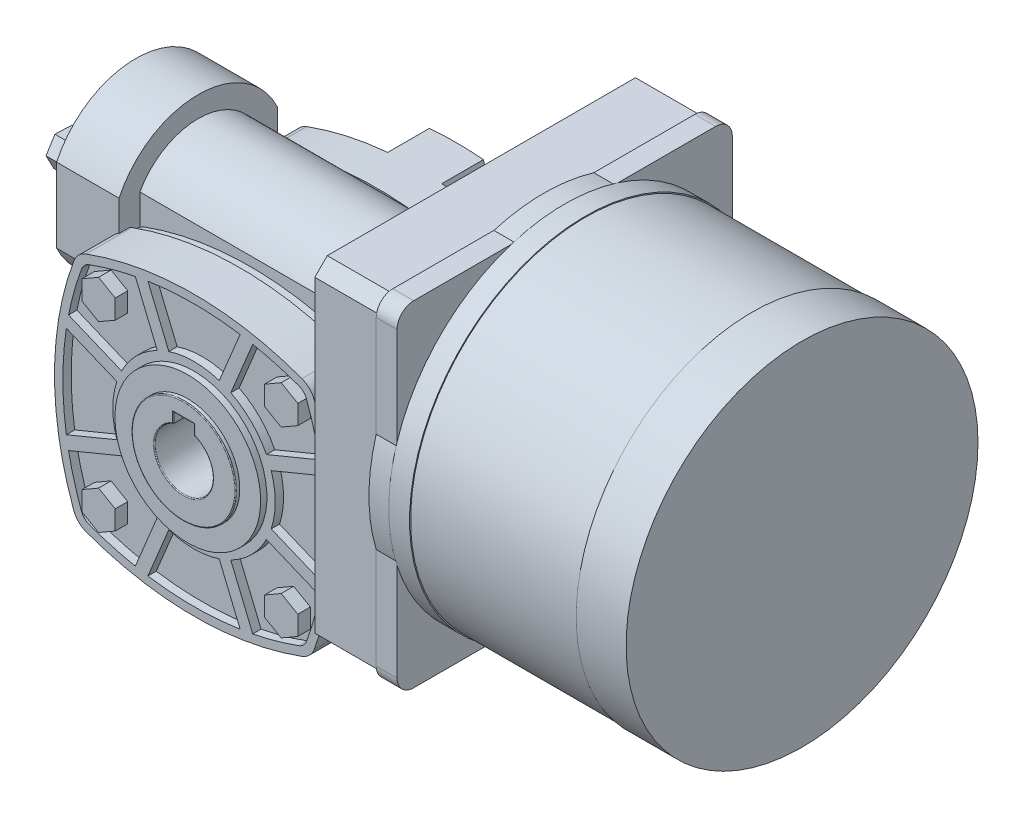
SolidWorks part; units mm, degrees
ref_plane "Piano frontale" through (0, 0, 0) normal (0, 0, 1) x (1, 0, 0)
ref_plane "Piano superiore" through (0, 0, 0) normal (0, 1, 0) x (1, 0, 0)
ref_plane "Piano destro" through (0, 0, 0) normal (1, 0, 0) x (0, 0, -1)
sketch "Schizzo1" plane through (0, 0, 0) normal (0, 0, 1) x (1, 0, 0)
  line L0 (0, 58.1474) -> (0, -73.5071) construction
  line L1 (33.5, 58.1474) -> (33.5, -73.5071) construction
  line L2 (55.3795, 33.5) -> (-59.3281, 33.5) construction
  line L3 (49.0237, -33.5) -> (-57.2095, -33.5) construction
  line L4 (-33.5, 58.1474) -> (-33.5, -69.2067) construction
  line L5 (-166.5974, 0) -> (96.1809, 0) construction
  circle A0 centre (0, 0) radius 7
  arc A1 (25.9159, 28.8802) -> (-25.9159, 28.8802) centre (0, -41.5) ccw
  arc A2 (25.9159, -28.8802) -> (-25.9159, -28.8802) centre (0, 41.5) cw
  arc A3 (28.8802, -25.9159) -> (28.8802, 25.9159) centre (-41.5, 0) ccw
  arc A4 (-28.8802, -25.9159) -> (-28.8802, 25.9159) centre (41.5, 0) cw
  arc A5 (-28.8802, 25.9159) -> (-25.9159, 28.8802) centre (-24.1882, 24.1882) cw
  arc A6 (25.9159, 28.8802) -> (28.8802, 25.9159) centre (24.1882, 24.1882) cw
  arc A7 (25.9159, -28.8802) -> (28.8802, -25.9159) centre (24.1882, -24.1882) ccw
  arc A8 (-28.8802, -25.9159) -> (-25.9159, -28.8802) centre (-24.1882, -24.1882) ccw
  point P17 (-28.0551, 28.0551)
  point P20 (28.0551, 28.0551)
  point P23 (28.0551, -28.0551)
  point P26 (-28.0551, -28.0551)
  dimension "D5" = 14
  dimension "D6" = 150
  dimension "D1" = 150
  dimension "D4" = 5
  dimension "D2" = 67
  dimension "D3" = 67
extrude "Estrusione1" add sketch "Schizzo1" along normal mid plane 51
sketch "Schizzo2" plane through (0, 0, -25.5) normal (0, 0, -1) x (-1, 0, 0)
  circle A0 centre (0, 0) radius 7 construction
  circle A1 centre (0, 0) radius 7
  arc A8 (28.8802, 25.9159) -> (25.9159, 28.8802) centre (24.1882, 24.1882) ccw
  arc A9 (25.9159, 28.8802) -> (-25.9159, 28.8802) centre (0, -41.5) ccw
  arc A10 (-25.9159, 28.8802) -> (-28.8802, 25.9159) centre (-24.1882, 24.1882) ccw
  arc A11 (-28.8802, 25.9159) -> (-28.8802, -25.9159) centre (41.5, 0) ccw
  arc A12 (-28.8802, -25.9159) -> (-25.9159, -28.8802) centre (-24.1882, -24.1882) ccw
  arc A13 (-25.9159, -28.8802) -> (25.9159, -28.8802) centre (0, 41.5) ccw
  arc A14 (25.9159, -28.8802) -> (28.8802, -25.9159) centre (24.1882, -24.1882) ccw
  arc A15 (28.8802, -25.9159) -> (28.8802, 25.9159) centre (-41.5, 0) ccw
  arc A16 (28.8802, 25.9159) -> (25.9159, 28.8802) centre (24.1882, 24.1882) ccw
  arc A17 (25.9159, 28.8802) -> (-25.9159, 28.8802) centre (0, -41.5) ccw
  arc A18 (-25.9159, 28.8802) -> (-28.8802, 25.9159) centre (-24.1882, 24.1882) ccw
  arc A19 (-28.8802, 25.9159) -> (-28.8802, -25.9159) centre (41.5, 0) ccw
  arc A20 (-28.8802, -25.9159) -> (-25.9159, -28.8802) centre (-24.1882, -24.1882) ccw
  arc A21 (-25.9159, -28.8802) -> (25.9159, -28.8802) centre (0, 41.5) ccw
  arc A22 (25.9159, -28.8802) -> (28.8802, -25.9159) centre (24.1882, -24.1882) ccw
  arc A23 (28.8802, -25.9159) -> (28.8802, 25.9159) centre (-41.5, 0) ccw
  dimension "D1" = 0
extrude "Estrusione2" add sketch "Schizzo2" along normal blind 10
sketch "Schizzo3" plane through (0, 0, -35.5) normal (0, 0, -1) x (-1, 0, 0)
  line L0 (0, 44.6694) -> (0, -48.5916) construction
  line L1 (-47.0663, 0) -> (53.3854, 0) construction
  line L2 (-6.5, 33.2178) -> (-9.8289, 20.794)
  line L3 (6.5, 33.2178) -> (9.8289, 20.794)
  line L4 (-6.5, -33.2178) -> (-9.8289, -20.794)
  line L5 (6.5, -33.2178) -> (9.8289, -20.794)
  line L6 (33.2178, 6.5) -> (20.794, 9.8289)
  line L7 (33.2178, -6.5) -> (20.794, -9.8289)
  line L8 (-33.2178, -6.5) -> (-20.794, -9.8289)
  line L9 (-33.2178, 6.5) -> (-20.794, 9.8289)
  circle A0 centre (0, 0) radius 27.5 construction
  circle A1 centre (0, 27.5) radius 2.5
  circle A2 centre (0, -27.5) radius 2.5
  circle A3 centre (-27.5, 0) radius 2.5
  circle A4 centre (27.5, 0) radius 2.5
  circle A5 centre (0, 0) radius 21
  arc A6 (20.794, 9.8289) -> (9.8289, 20.794) centre (0, 0) ccw
  arc A7 (25.9159, 28.8802) -> (-25.9159, 28.8802) centre (0, -41.5) ccw construction
  arc A8 (-6.5, 33.2178) -> (-25.9159, 28.8802) centre (0, -41.5) ccw
  arc A9 (6.5, -33.2178) -> (25.9159, -28.8802) centre (0, 41.5) ccw
  arc A10 (-20.794, -9.8289) -> (-9.8289, -20.794) centre (0, 0) ccw
  arc A11 (28.8802, -25.9159) -> (28.8802, 25.9159) centre (-41.5, 0) ccw construction
  arc A12 (33.2178, 6.5) -> (28.8802, 25.9159) centre (-41.5, 0) ccw
  arc A13 (28.8802, -25.9159) -> (33.2178, -6.5) centre (-41.5, 0) ccw
  arc A16 (28.8802, 25.9159) -> (25.9159, 28.8802) centre (24.1882, 24.1882) ccw construction
  arc A17 (25.9159, 28.8802) -> (6.5, 33.2178) centre (0, -41.5) ccw
  arc A18 (28.8802, 25.9159) -> (25.9159, 28.8802) centre (24.1882, 24.1882) ccw
  arc A19 (-25.9159, -28.8802) -> (25.9159, -28.8802) centre (0, 41.5) ccw construction
  arc A20 (25.9159, -28.8802) -> (28.8802, -25.9159) centre (24.1882, -24.1882) ccw construction
  arc A21 (-25.9159, -28.8802) -> (-6.5, -33.2178) centre (0, 41.5) ccw
  arc A22 (25.9159, -28.8802) -> (28.8802, -25.9159) centre (24.1882, -24.1882) ccw
  arc A23 (-25.9159, 28.8802) -> (-28.8802, 25.9159) centre (-24.1882, 24.1882) ccw construction
  arc A24 (-28.8802, 25.9159) -> (-28.8802, -25.9159) centre (41.5, 0) ccw construction
  arc A25 (-28.8802, -25.9159) -> (-25.9159, -28.8802) centre (-24.1882, -24.1882) ccw construction
  arc A26 (-25.9159, 28.8802) -> (-28.8802, 25.9159) centre (-24.1882, 24.1882) ccw
  arc A27 (-28.8802, 25.9159) -> (-33.2178, 6.5) centre (41.5, 0) ccw
  arc A28 (-28.8802, -25.9159) -> (-25.9159, -28.8802) centre (-24.1882, -24.1882) ccw
  circle A29 centre (0, 0) radius 7 construction
  arc A30 (-33.2178, -6.5) -> (-28.8802, -25.9159) centre (41.5, 0) ccw
  arc A31 (9.8289, -20.794) -> (20.794, -9.8289) centre (0, 0) ccw
  arc A33 (-9.8289, 20.794) -> (-20.794, 9.8289) centre (0, 0) ccw
  circle A34 centre (0, 0) radius 7
  dimension "D1" = 55
  dimension "D2" = 5
  dimension "D3" = 5
  dimension "D4" = 46
  dimension "D5" = 42
  dimension "D6" = 6.5
  dimension "D7" = 15
  dimension "D8" = 6.5
  dimension "D9" = 15
extrude "Taglio-Estrusione1" cut sketch "Schizzo3" against normal blind 10
sketch "Schizzo4" plane through (0, 0, -25.5) normal (0, 0, -1) x (-1, 0, 0)
  circle A0 centre (0, 0) radius 12.5
  circle A1 centre (0, 0) radius 7 construction
  circle A2 centre (0, 0) radius 7
  dimension "D1" = 25
extrude "Estrusione3" add sketch "Schizzo4" along normal blind 6
sketch "Schizzo5" plane through (0, 0, -31.5) normal (0, 0, -1) x (-1, 0, 0)
  line L0 (0, 18.2844) -> (0, -17.5278) construction
  line L1 (-16.1407, 0) -> (17.78, 0) construction
  line L3 (-2.5, 9) -> (2.5, 9)
  line L4 (-2.5, 9) -> (-2.5, 0)
  line L5 (-2.5, 0) -> (2.5, 0)
  line L6 (2.5, 9) -> (2.5, 0)
  dimension "D1" = 5
  dimension "D2" = 2.5
  dimension "D3" = 9
extrude "Taglio-Estrusione2" cut sketch "Schizzo5" against normal through all
fillet "Raccordo1" radius 0.2 2 edges at (-12.5, 0, -31.5) (0, -7, -31.5)
sketch "Schizzo6" plane through (0, 0, -25.5) normal (0, 0, -1) x (-1, 0, 0)
  line L0 (-42.7943, 42.7943) -> (48.4599, -48.4599) construction
  line L1 (0, 69.45) -> (0, -50.3495) construction
  line L2 (-53.2227, 0) -> (65.2745, 0) construction
  line L3 (25.9203, 19.6109) -> (21.9203, 17.3015)
  line L4 (-21.9203, 17.3015) -> (-17.9203, 19.6109)
  line L5 (-17.9203, 19.6109) -> (-17.9203, 24.2297)
  line L6 (-17.9203, 24.2297) -> (-21.9203, 26.5391)
  line L7 (-21.9203, 26.5391) -> (-25.9203, 24.2297)
  line L8 (-25.9203, 24.2297) -> (-25.9203, 19.6109)
  line L9 (-25.9203, 19.6109) -> (-21.9203, 17.3015)
  line L10 (25.9203, 24.2297) -> (25.9203, 19.6109)
  line L11 (21.9203, 26.5391) -> (25.9203, 24.2297)
  line L12 (17.9203, 24.2297) -> (21.9203, 26.5391)
  line L13 (17.9203, 19.6109) -> (17.9203, 24.2297)
  line L14 (21.9203, 17.3015) -> (17.9203, 19.6109)
  line L15 (21.9203, -17.3015) -> (17.9203, -19.6109)
  line L16 (17.9203, -19.6109) -> (17.9203, -24.2297)
  line L17 (17.9203, -24.2297) -> (21.9203, -26.5391)
  line L18 (21.9203, -26.5391) -> (25.9203, -24.2297)
  line L19 (25.9203, -24.2297) -> (25.9203, -19.6109)
  line L20 (-25.9203, -19.6109) -> (-21.9203, -17.3015)
  line L21 (-25.9203, -24.2297) -> (-25.9203, -19.6109)
  line L22 (-21.9203, -26.5391) -> (-25.9203, -24.2297)
  line L23 (-17.9203, -24.2297) -> (-21.9203, -26.5391)
  line L24 (-17.9203, -19.6109) -> (-17.9203, -24.2297)
  line L25 (-21.9203, -17.3015) -> (-17.9203, -19.6109)
  line L26 (25.9203, -19.6109) -> (21.9203, -17.3015)
  circle A0 centre (0, 0) radius 31 construction
  circle A1 centre (-21.9203, 21.9203) radius 4 construction
  circle A2 centre (21.9203, 21.9203) radius 4 construction
  circle A3 centre (21.9203, -21.9203) radius 4 construction
  circle A4 centre (-21.9203, -21.9203) radius 4 construction
  dimension "D1" = 62
  dimension "D2" = 45
  dimension "D3" = 8
extrude "Estrusione4" add sketch "Schizzo6" along normal blind 3
sketch "Schizzo7" plane through (0, 0, 25.5) normal (0, 0, 1) x (1, 0, 0)
  circle A0 centre (0, 0) radius 12.5
  circle A1 centre (0, 0) radius 17.5
  dimension "D1" = 35
  dimension "D2" = 25
extrude "Estrusione5" add sketch "Schizzo7" along normal blind 3.5
sketch "Schizzo8" plane through (0, 0, 25.5) normal (0, 0, 1) x (1, 0, 0)
  line L0 (2.5, 9) -> (2.5, 6.5383) construction
  line L1 (-2.5, 9) -> (2.5, 9) construction
  line L2 (-2.5, 6.5383) -> (-2.5, 9) construction
  line L3 (2.5, 9) -> (2.5, 6.5383)
  line L4 (-2.5, 9) -> (2.5, 9)
  line L5 (-2.5, 6.5383) -> (-2.5, 9)
  circle A0 centre (0, 0) radius 12.5 construction
  circle A1 centre (0, 0) radius 12.5
  arc A2 (-2.5, 6.5383) -> (2.5, 6.5383) centre (0, 0) ccw construction
  arc A3 (-2.5, 6.5383) -> (2.5, 6.5383) centre (0, 0) ccw
extrude "Estrusione6" add sketch "Schizzo8" along normal blind 4.5
fillet "Raccordo2" radius 0.2 5 edges at (0, -7, 30) (2.5, 7.7692, 30) (0, 9, 30) (-2.5, 7.7692, 30) (12.5, 0, 30)
sketch "Schizzo9" plane through (0, 0, 25.5) normal (0, 0, 1) x (1, 0, 0)
  line L0 (0, 35.6861) -> (0, -36.4427) construction
  line L1 (-41.865, 0) -> (44.5131, 0) construction
  line L2 (-34.3869, 34.3869) -> (33.9315, -33.9315) construction
  line L3 (-15.1925, 36.6781) -> (14.9737, -36.1497) construction
  line L4 (-14.1018, 30.125) -> (-8.826, 17.3882)
  line L5 (11.0742, 30.6551) -> (6.0544, 18.5363)
  line L6 (-11.0742, 30.6551) -> (-6.0544, 18.5363)
  line L7 (14.1018, 30.125) -> (8.826, 17.3882)
  line L8 (14.1018, -30.125) -> (8.826, -17.3882)
  line L9 (-11.0742, -30.6551) -> (-6.0544, -18.5363)
  line L10 (11.0742, -30.6551) -> (6.0544, -18.5363)
  line L11 (-14.1018, -30.125) -> (-8.826, -17.3882)
  line L12 (-30.125, 14.1018) -> (-17.3882, 8.826)
  line L13 (-30.6551, 11.0742) -> (-18.5363, 6.0544)
  line L14 (-30.6551, -11.0742) -> (-18.5363, -6.0544)
  line L15 (-30.125, -14.1018) -> (-17.3882, -8.826)
  line L16 (30.125, -14.1018) -> (17.3882, -8.826)
  line L17 (30.6551, -11.0742) -> (18.5363, -6.0544)
  line L18 (30.6551, 11.0742) -> (18.5363, 6.0544)
  line L19 (30.125, 14.1018) -> (17.3882, 8.826)
  circle A0 centre (0, 0) radius 17.5 construction
  circle A1 centre (0, 0) radius 17.5
  arc A2 (-8.826, 17.3882) -> (-17.3882, 8.826) centre (0, 0) ccw
  circle A3 centre (0, 0) radius 19.5 construction
  arc A12 (-14.1018, 30.125) -> (-25.2248, 27.0034) centre (0, -41.5) ccw
  arc A13 (11.0742, 30.6551) -> (-11.0742, 30.6551) centre (0, -41.5) ccw
  arc A14 (6.0544, 18.5363) -> (-6.0544, 18.5363) centre (0, 0) ccw
  arc A15 (-6.0544, -18.5363) -> (6.0544, -18.5363) centre (0, 0) ccw
  arc A16 (-11.0742, -30.6551) -> (11.0742, -30.6551) centre (0, 41.5) ccw
  arc A17 (14.1018, -30.125) -> (25.2248, -27.0034) centre (0, 41.5) ccw
  arc A18 (8.826, -17.3882) -> (17.3882, -8.826) centre (0, 0) ccw
  arc A19 (17.3882, 8.826) -> (8.826, 17.3882) centre (0, 0) ccw
  arc A20 (-25.2248, 27.0034) -> (-27.0034, 25.2248) centre (-24.1882, 24.1882) ccw
  arc A21 (-27.0034, 25.2248) -> (-27.0034, -25.2248) centre (41.5, 0) ccw
  arc A22 (-27.0034, -25.2248) -> (-25.2248, -27.0034) centre (-24.1882, -24.1882) ccw
  arc A23 (-25.2248, -27.0034) -> (25.2248, -27.0034) centre (0, 41.5) ccw
  arc A24 (25.2248, -27.0034) -> (27.0034, -25.2248) centre (24.1882, -24.1882) ccw
  arc A25 (27.0034, -25.2248) -> (27.0034, 25.2248) centre (-41.5, 0) ccw
  arc A26 (27.0034, 25.2248) -> (25.2248, 27.0034) centre (24.1882, 24.1882) ccw
  arc A27 (25.2248, 27.0034) -> (-25.2248, 27.0034) centre (0, -41.5) ccw
  arc A28 (-25.2248, 27.0034) -> (-27.0034, 25.2248) centre (-24.1882, 24.1882) ccw
  arc A29 (-27.0034, 25.2248) -> (-30.125, 14.1018) centre (41.5, 0) ccw
  arc A30 (-27.0034, -25.2248) -> (-25.2248, -27.0034) centre (-24.1882, -24.1882) ccw
  arc A31 (-25.2248, -27.0034) -> (-14.1018, -30.125) centre (0, 41.5) ccw
  arc A32 (25.2248, -27.0034) -> (27.0034, -25.2248) centre (24.1882, -24.1882) ccw
  arc A33 (27.0034, -25.2248) -> (30.125, -14.1018) centre (-41.5, 0) ccw
  arc A34 (27.0034, 25.2248) -> (25.2248, 27.0034) centre (24.1882, 24.1882) ccw
  arc A35 (25.2248, 27.0034) -> (14.1018, 30.125) centre (0, -41.5) ccw
  arc A36 (-25.9159, 28.8802) -> (-28.8802, 25.9159) centre (-24.1882, 24.1882) ccw
  arc A37 (-28.8802, 25.9159) -> (-28.8802, -25.9159) centre (41.5, 0) ccw
  arc A38 (-28.8802, -25.9159) -> (-25.9159, -28.8802) centre (-24.1882, -24.1882) ccw
  arc A39 (-25.9159, -28.8802) -> (25.9159, -28.8802) centre (0, 41.5) ccw
  arc A40 (25.9159, -28.8802) -> (28.8802, -25.9159) centre (24.1882, -24.1882) ccw
  arc A41 (28.8802, -25.9159) -> (28.8802, 25.9159) centre (-41.5, 0) ccw
  arc A42 (28.8802, 25.9159) -> (25.9159, 28.8802) centre (24.1882, 24.1882) ccw
  arc A43 (25.9159, 28.8802) -> (-25.9159, 28.8802) centre (0, -41.5) ccw
  arc A44 (-25.9159, 28.8802) -> (-28.8802, 25.9159) centre (-24.1882, 24.1882) ccw
  arc A45 (-28.8802, 25.9159) -> (-28.8802, -25.9159) centre (41.5, 0) ccw
  arc A46 (-28.8802, -25.9159) -> (-25.9159, -28.8802) centre (-24.1882, -24.1882) ccw
  arc A47 (-25.9159, -28.8802) -> (25.9159, -28.8802) centre (0, 41.5) ccw
  arc A48 (25.9159, -28.8802) -> (28.8802, -25.9159) centre (24.1882, -24.1882) ccw
  arc A49 (28.8802, -25.9159) -> (28.8802, 25.9159) centre (-41.5, 0) ccw
  arc A50 (28.8802, 25.9159) -> (25.9159, 28.8802) centre (24.1882, 24.1882) ccw
  arc A51 (25.9159, 28.8802) -> (-25.9159, 28.8802) centre (0, -41.5) ccw
  arc A52 (18.5363, -6.0544) -> (18.5363, 6.0544) centre (0, 0) ccw
  arc A53 (-17.3882, -8.826) -> (-8.826, -17.3882) centre (0, 0) ccw
  arc A54 (-18.5363, 6.0544) -> (-18.5363, -6.0544) centre (0, 0) ccw
  arc A55 (-30.6551, 11.0742) -> (-30.6551, -11.0742) centre (41.5, 0) ccw
  arc A56 (-30.125, -14.1018) -> (-27.0034, -25.2248) centre (41.5, 0) ccw
  arc A57 (30.6551, -11.0742) -> (30.6551, 11.0742) centre (-41.5, 0) ccw
  arc A58 (30.125, 14.1018) -> (27.0034, 25.2248) centre (-41.5, 0) ccw
  dimension "D3" = 22.5
  dimension "D4" = 3
  dimension "D5" = 1.5
  dimension "D1" = 2
  dimension "D6" = 2
  dimension "D7" = 0
extrude "Estrusione7" add sketch "Schizzo9" along normal blind 2
sketch "Schizzo11" plane through (0, 0, 0) normal (0, 0, 1) x (1, 0, 0)
  arc A16 (25.5703, 27.9418) -> (-25.5703, 27.9418) centre (0, -41.5) ccw
  arc A17 (-25.5703, 27.9418) -> (-27.9418, 25.5703) centre (-24.1882, 24.1882) ccw
  arc A18 (-27.9418, 25.5703) -> (-27.9418, -25.5703) centre (41.5, 0) ccw
  arc A19 (-27.9418, -25.5703) -> (-25.5703, -27.9418) centre (-24.1882, -24.1882) ccw
  arc A20 (-25.5703, -27.9418) -> (25.5703, -27.9418) centre (0, 41.5) ccw
  arc A21 (25.5703, -27.9418) -> (27.9418, -25.5703) centre (24.1882, -24.1882) ccw
  arc A22 (27.9418, -25.5703) -> (27.9418, 25.5703) centre (-41.5, 0) ccw
  arc A23 (27.9418, 25.5703) -> (25.5703, 27.9418) centre (24.1882, 24.1882) ccw
  arc A24 (25.5703, 27.9418) -> (-25.5703, 27.9418) centre (0, -41.5) ccw
  arc A25 (-25.5703, 27.9418) -> (-27.9418, 25.5703) centre (-24.1882, 24.1882) ccw
  arc A26 (-27.9418, 25.5703) -> (-27.9418, -25.5703) centre (41.5, 0) ccw
  arc A27 (-27.9418, -25.5703) -> (-25.5703, -27.9418) centre (-24.1882, -24.1882) ccw
  arc A28 (-25.5703, -27.9418) -> (25.5703, -27.9418) centre (0, 41.5) ccw
  arc A29 (25.5703, -27.9418) -> (27.9418, -25.5703) centre (24.1882, -24.1882) ccw
  arc A30 (27.9418, -25.5703) -> (27.9418, 25.5703) centre (-41.5, 0) ccw
  arc A31 (27.9418, 25.5703) -> (25.5703, 27.9418) centre (24.1882, 24.1882) ccw
  arc A40 (36.6278, 57.9706) -> (-36.6278, 57.9706) centre (0, -41.5) ccw
  arc A41 (-36.6278, 57.9706) -> (-57.9706, 36.6278) centre (-24.1882, 24.1882) ccw
  arc A42 (-57.9706, 36.6278) -> (-57.9706, -36.6278) centre (41.5, 0) ccw
  arc A43 (-57.9706, -36.6278) -> (-36.6278, -57.9706) centre (-24.1882, -24.1882) ccw
  arc A44 (-36.6278, -57.9706) -> (36.6278, -57.9706) centre (0, 41.5) ccw
  arc A45 (36.6278, -57.9706) -> (57.9706, -36.6278) centre (24.1882, -24.1882) ccw
  arc A46 (57.9706, -36.6278) -> (57.9706, 36.6278) centre (-41.5, 0) ccw
  arc A47 (57.9706, 36.6278) -> (36.6278, 57.9706) centre (24.1882, 24.1882) ccw
  arc A48 (36.6278, 57.9706) -> (-36.6278, 57.9706) centre (0, -41.5) ccw
  arc A49 (-36.6278, 57.9706) -> (-57.9706, 36.6278) centre (-24.1882, 24.1882) ccw
  arc A50 (-57.9706, 36.6278) -> (-57.9706, -36.6278) centre (41.5, 0) ccw
  arc A51 (-57.9706, -36.6278) -> (-36.6278, -57.9706) centre (-24.1882, -24.1882) ccw
  arc A52 (-36.6278, -57.9706) -> (36.6278, -57.9706) centre (0, 41.5) ccw
  arc A53 (36.6278, -57.9706) -> (57.9706, -36.6278) centre (24.1882, -24.1882) ccw
  arc A54 (57.9706, -36.6278) -> (57.9706, 36.6278) centre (-41.5, 0) ccw
  arc A55 (57.9706, 36.6278) -> (36.6278, 57.9706) centre (24.1882, 24.1882) ccw
  dimension "D1" = 1
  dimension "D2" = 31
extrude "Taglio-Estrusione3" cut sketch "Schizzo11" against normal blind 15 from offset 1.5 offset against normal yes
sketch "Schizzo12" plane through (0, 0, 0) normal (0, 0, 1) x (1, 0, 0)
  arc A16 (25.5703, 27.9418) -> (-25.5703, 27.9418) centre (0, -41.5) ccw
  arc A17 (-25.5703, 27.9418) -> (-27.9418, 25.5703) centre (-24.1882, 24.1882) ccw
  arc A18 (-27.9418, 25.5703) -> (-27.9418, -25.5703) centre (41.5, 0) ccw
  arc A19 (-27.9418, -25.5703) -> (-25.5703, -27.9418) centre (-24.1882, -24.1882) ccw
  arc A20 (-25.5703, -27.9418) -> (25.5703, -27.9418) centre (0, 41.5) ccw
  arc A21 (25.5703, -27.9418) -> (27.9418, -25.5703) centre (24.1882, -24.1882) ccw
  arc A22 (27.9418, -25.5703) -> (27.9418, 25.5703) centre (-41.5, 0) ccw
  arc A23 (27.9418, 25.5703) -> (25.5703, 27.9418) centre (24.1882, 24.1882) ccw
  arc A24 (25.5703, 27.9418) -> (-25.5703, 27.9418) centre (0, -41.5) ccw
  arc A25 (-25.5703, 27.9418) -> (-27.9418, 25.5703) centre (-24.1882, 24.1882) ccw
  arc A26 (-27.9418, 25.5703) -> (-27.9418, -25.5703) centre (41.5, 0) ccw
  arc A27 (-27.9418, -25.5703) -> (-25.5703, -27.9418) centre (-24.1882, -24.1882) ccw
  arc A28 (-25.5703, -27.9418) -> (25.5703, -27.9418) centre (0, 41.5) ccw
  arc A29 (25.5703, -27.9418) -> (27.9418, -25.5703) centre (24.1882, -24.1882) ccw
  arc A30 (27.9418, -25.5703) -> (27.9418, 25.5703) centre (-41.5, 0) ccw
  arc A31 (27.9418, 25.5703) -> (25.5703, 27.9418) centre (24.1882, 24.1882) ccw
  arc A40 (29.7169, 39.2026) -> (-29.7169, 39.2026) centre (0, -41.5) ccw
  arc A41 (-29.7169, 39.2026) -> (-39.2026, 29.7169) centre (-24.1882, 24.1882) ccw
  arc A42 (-39.2026, 29.7169) -> (-39.2026, -29.7169) centre (41.5, 0) ccw
  arc A43 (-39.2026, -29.7169) -> (-29.7169, -39.2026) centre (-24.1882, -24.1882) ccw
  arc A44 (-29.7169, -39.2026) -> (29.7169, -39.2026) centre (0, 41.5) ccw
  arc A45 (29.7169, -39.2026) -> (39.2026, -29.7169) centre (24.1882, -24.1882) ccw
  arc A46 (39.2026, -29.7169) -> (39.2026, 29.7169) centre (-41.5, 0) ccw
  arc A47 (39.2026, 29.7169) -> (29.7169, 39.2026) centre (24.1882, 24.1882) ccw
  arc A48 (29.7169, 39.2026) -> (-29.7169, 39.2026) centre (0, -41.5) ccw
  arc A49 (-29.7169, 39.2026) -> (-39.2026, 29.7169) centre (-24.1882, 24.1882) ccw
  arc A50 (-39.2026, 29.7169) -> (-39.2026, -29.7169) centre (41.5, 0) ccw
  arc A51 (-39.2026, -29.7169) -> (-29.7169, -39.2026) centre (-24.1882, -24.1882) ccw
  arc A52 (-29.7169, -39.2026) -> (29.7169, -39.2026) centre (0, 41.5) ccw
  arc A53 (29.7169, -39.2026) -> (39.2026, -29.7169) centre (24.1882, -24.1882) ccw
  arc A54 (39.2026, -29.7169) -> (39.2026, 29.7169) centre (-41.5, 0) ccw
  arc A55 (39.2026, 29.7169) -> (29.7169, 39.2026) centre (24.1882, 24.1882) ccw
  dimension "D1" = 1
  dimension "D2" = 11
extrude "Taglio-Estrusione4" cut sketch "Schizzo12" along normal blind 15 from offset 1.5
sketch "Schizzo13" plane through (0, 0, 0) normal (1, 0, 0) x (0, 0, -1)
  line L0 (0, 70.0765) -> (0, -61.4477) construction
  line L3 (14, 34.746) -> (14, 19.254)
  line L5 (-14, 34.746) -> (-14, 19.254)
  arc A0 (-14, 19.254) -> (14, 19.254) centre (0, 27) ccw
  arc A1 (14, 34.746) -> (-14, 34.746) centre (0, 27) ccw
  dimension "D1" = 32
  dimension "D2" = 27
  dimension "D3" = 14
  dimension "D4" = 28
extrude "Estrusione8" add sketch "Schizzo13" against normal blind 41.5 and the other way blind 41.5
sketch "Schizzo15" plane through (-41.5, 0, 0) normal (-1, 0, 0) x (0, 0, 1)
  line L6 (19, 18.0557) -> (19, 35.9443)
  line L7 (-19, 35.9443) -> (-19, 18.0557)
  line L8 (19, 18.0557) -> (19, 35.9443)
  line L9 (-19, 35.9443) -> (-19, 18.0557)
  arc A6 (-19, 18.0557) -> (19, 18.0557) centre (0, 27) ccw
  arc A7 (19, 35.9443) -> (-19, 35.9443) centre (0, 27) ccw
  arc A8 (-19, 18.0557) -> (19, 18.0557) centre (0, 27) ccw
  arc A9 (19, 35.9443) -> (-19, 35.9443) centre (0, 27) ccw
  dimension "D1" = 5
extrude "Estrusione9" add sketch "Schizzo15" against normal blind 15
sketch "Schizzo16" plane through (41.5, 0, 0) normal (1, 0, 0) x (0, 0, -1)
  line L1 (-16, 46) -> (16, 46)
  line L2 (-19, 43) -> (-19, 11)
  line L3 (-16, 8) -> (16, 8)
  line L4 (19, 43) -> (19, 11)
  line L6 (0, 51.5796) -> (0, -11.6169) construction
  line L7 (-33.6033, 27) -> (42.7846, 27) construction
  arc A0 (16, 46) -> (19, 43) centre (16, 43) cw
  arc A1 (-16, 46) -> (-19, 43) centre (-16, 43) ccw
  arc A2 (-19, 11) -> (-16, 8) centre (-16, 11) ccw
  arc A3 (16, 8) -> (19, 11) centre (16, 11) ccw
  dimension "D5" = 3
  dimension "D1" = 38
  dimension "D2" = 38
  dimension "D3" = 19
  dimension "D4" = 19
extrude "Estrusione10" add sketch "Schizzo16" against normal blind 15
chamfer "Smusso1" distance 3 angle 45 5 edges at (26.5, 35.8108, -19) (26.5, 35.8108, 19) (26.5, 45.1213, -18.1213) (26.5, 45.1213, 18.1213) (26.5, 46, 0)
sketch "Schizzo17" plane through (-41.5, 0, 0) normal (-1, 0, 0) x (0, 0, 1)
  line L0 (0, 57.3899) -> (0, -44.657) construction
  line L1 (-46.4844, 27) -> (46.7273, 27) construction
  line L2 (-31.3971, 45.1271) -> (62.5543, -9.1158) construction
  line L3 (16.6579, 31.9541) -> (12.6194, 31.8009)
  line L4 (-12.6194, 31.8009) -> (-10.4674, 35.2218)
  line L5 (-10.4674, 35.2218) -> (-12.354, 38.7959)
  line L6 (-12.354, 38.7959) -> (-16.3925, 38.9491)
  line L7 (-16.3925, 38.9491) -> (-18.5445, 35.5282)
  line L8 (-18.5445, 35.5282) -> (-16.6579, 31.9541)
  line L9 (-16.6579, 31.9541) -> (-12.6194, 31.8009)
  line L10 (18.5445, 35.5282) -> (16.6579, 31.9541)
  line L11 (16.3925, 38.9491) -> (18.5445, 35.5282)
  line L12 (12.354, 38.7959) -> (16.3925, 38.9491)
  line L13 (10.4674, 35.2218) -> (12.354, 38.7959)
  line L14 (12.6194, 31.8009) -> (10.4674, 35.2218)
  line L16 (0, 6.2085) -> (3.5, 8.2293)
  line L17 (3.5, 8.2293) -> (3.5, 12.2707)
  line L18 (3.5, 12.2707) -> (0, 14.2915)
  line L19 (0, 14.2915) -> (-3.5, 12.2707)
  line L20 (-3.5, 12.2707) -> (-3.5, 8.2293)
  line L21 (-3.5, 8.2293) -> (0, 6.2085)
  circle A0 centre (-14.5059, 35.375) radius 3.5 construction
  circle A1 centre (14.5059, 35.375) radius 3.5 construction
  circle A2 centre (0, 10.25) radius 3.5 construction
  circle A3 centre (0, 27) radius 16.75 construction
  dimension "D4" = 33.5
  dimension "D1" = 60
  dimension "D2" = 7
  dimension "D3" = 7
extrude "Estrusione11" add sketch "Schizzo17" along normal blind 3
sketch "Schizzo18" plane through (0, 0, 25.5) normal (0, 0, 1) x (1, 0, 0)
  line L0 (-21.9203, -26.5391) -> (-25.9203, -24.2297) construction
  line L1 (-25.9203, -24.2297) -> (-25.9203, -19.6109) construction
  line L2 (-25.9203, -19.6109) -> (-21.9203, -17.3015) construction
  line L3 (-21.9203, -17.3015) -> (-17.9203, -19.6109) construction
  line L4 (-17.9203, -19.6109) -> (-17.9203, -24.2297) construction
  line L5 (-17.9203, -24.2297) -> (-21.9203, -26.5391) construction
  line L6 (25.9203, -19.6109) -> (25.9203, -24.2297) construction
  line L7 (25.9203, -24.2297) -> (21.9203, -26.5391) construction
  line L8 (21.9203, -26.5391) -> (17.9203, -24.2297) construction
  line L9 (17.9203, -24.2297) -> (17.9203, -19.6109) construction
  line L10 (17.9203, -19.6109) -> (21.9203, -17.3015) construction
  line L11 (21.9203, -17.3015) -> (25.9203, -19.6109) construction
  line L12 (21.9203, 26.5391) -> (25.9203, 24.2297) construction
  line L13 (25.9203, 24.2297) -> (25.9203, 19.6109) construction
  line L14 (25.9203, 19.6109) -> (21.9203, 17.3015) construction
  line L15 (21.9203, 17.3015) -> (17.9203, 19.6109) construction
  line L16 (17.9203, 19.6109) -> (17.9203, 24.2297) construction
  line L17 (17.9203, 24.2297) -> (21.9203, 26.5391) construction
  line L18 (-21.9203, 17.3015) -> (-25.9203, 19.6109) construction
  line L19 (-17.9203, 19.6109) -> (-21.9203, 17.3015) construction
  line L20 (-17.9203, 24.2297) -> (-17.9203, 19.6109) construction
  line L21 (-21.9203, 26.5391) -> (-17.9203, 24.2297) construction
  line L22 (-25.9203, 24.2297) -> (-21.9203, 26.5391) construction
  line L23 (-25.9203, 19.6109) -> (-25.9203, 24.2297) construction
  line L24 (-21.9203, -26.5391) -> (-25.9203, -24.2297)
  line L25 (-25.9203, -24.2297) -> (-25.9203, -19.6109)
  line L26 (-25.9203, -19.6109) -> (-21.9203, -17.3015)
  line L27 (-21.9203, -17.3015) -> (-17.9203, -19.6109)
  line L28 (-17.9203, -19.6109) -> (-17.9203, -24.2297)
  line L29 (-17.9203, -24.2297) -> (-21.9203, -26.5391)
  line L30 (25.9203, -19.6109) -> (25.9203, -24.2297)
  line L31 (25.9203, -24.2297) -> (21.9203, -26.5391)
  line L32 (21.9203, -26.5391) -> (17.9203, -24.2297)
  line L33 (17.9203, -24.2297) -> (17.9203, -19.6109)
  line L34 (17.9203, -19.6109) -> (21.9203, -17.3015)
  line L35 (21.9203, -17.3015) -> (25.9203, -19.6109)
  line L36 (21.9203, 26.5391) -> (25.9203, 24.2297)
  line L37 (25.9203, 24.2297) -> (25.9203, 19.6109)
  line L38 (25.9203, 19.6109) -> (21.9203, 17.3015)
  line L39 (21.9203, 17.3015) -> (17.9203, 19.6109)
  line L40 (17.9203, 19.6109) -> (17.9203, 24.2297)
  line L41 (17.9203, 24.2297) -> (21.9203, 26.5391)
  line L42 (-21.9203, 17.3015) -> (-25.9203, 19.6109)
  line L43 (-17.9203, 19.6109) -> (-21.9203, 17.3015)
  line L44 (-17.9203, 24.2297) -> (-17.9203, 19.6109)
  line L45 (-21.9203, 26.5391) -> (-17.9203, 24.2297)
  line L46 (-25.9203, 24.2297) -> (-21.9203, 26.5391)
  line L47 (-25.9203, 19.6109) -> (-25.9203, 24.2297)
extrude "Estrusione12" add sketch "Schizzo18" along normal blind 3
sketch "Schizzo19" plane through (41.5, 0, 0) normal (1, 0, 0) x (0, 0, -1)
  line L0 (0, 93.4465) -> (0, -56.6817) construction
  line L1 (-46.5506, 27) -> (66.9998, 27) construction
  line L2 (37, 67) -> (40, 64)
  line L3 (-37, 67) -> (37, 67)
  line L4 (-40, 64) -> (-40, -10)
  line L5 (-37, -13) -> (37, -13)
  line L6 (40, 64) -> (40, -10)
  line L7 (-40, 64) -> (-37, 67)
  line L8 (-40, -10) -> (-37, -13)
  line L9 (37, -13) -> (40, -10)
  point P6 (-40, 67)
  point P7 (40, -13)
  point P8 (-40, -13)
  point P9 (40, 67)
  dimension "D1" = 80
  dimension "D2" = 80
  dimension "D3" = 40
  dimension "D4" = 40
extrude "Estrusione13" add sketch "Schizzo19" along normal blind 15
sketch "Schizzo20" plane through (56.5, 0, 0) normal (1, 0, 0) x (0, 0, -1)
  circle A0 centre (0, 27) radius 42
  dimension "D1" = 84
extrude "Estrusione14" add sketch "Schizzo20" along normal blind 62
sketch "Schizzo21" plane through (56.5, 0, 0) normal (1, 0, 0) x (0, 0, -1)
  line L2 (-36.25, 67.25) -> (36.25, 67.25)
  line L3 (-40.25, 63.25) -> (-40.25, -9.25)
  line L4 (-36.25, -13.25) -> (36.25, -13.25)
  line L8 (40.25, 63.25) -> (40.25, -9.25)
  circle A0 centre (0, 27) radius 42 construction
  arc A1 (36.25, 67.25) -> (40.25, 63.25) centre (36.25, 63.25) cw
  arc A2 (-36.25, 67.25) -> (-40.25, 63.25) centre (-36.25, 63.25) ccw
  arc A3 (-40.25, -9.25) -> (-36.25, -13.25) centre (-36.25, -9.25) ccw
  arc A4 (36.25, -13.25) -> (40.25, -9.25) centre (36.25, -9.25) ccw
  dimension "D2" = 40.25
  dimension "D5" = 4
  dimension "D1" = 40.25
  dimension "D3" = 80.5
  dimension "D4" = 80.5
extrude "Estrusione16" add sketch "Schizzo21" along normal blind 5
sketch "Schizzo23" plane through (61.5, 0, 0) normal (1, 0, 0) x (0, 0, -1)
  circle A2 centre (0, 27) radius 42.25
  circle A3 centre (0, 27) radius 42.25
  dimension "D1" = 0.25
extrude "Estrusione17" add sketch "Schizzo23" along normal blind 5
sketch "Schizzo24" plane through (118.5, 0, 0) normal (1, 0, 0) x (0, 0, -1)
  circle A0 centre (0, 27) radius 42.25 construction
  circle A1 centre (0, 27) radius 42.25
extrude "Estrusione18" add sketch "Schizzo24" against normal blind 12
